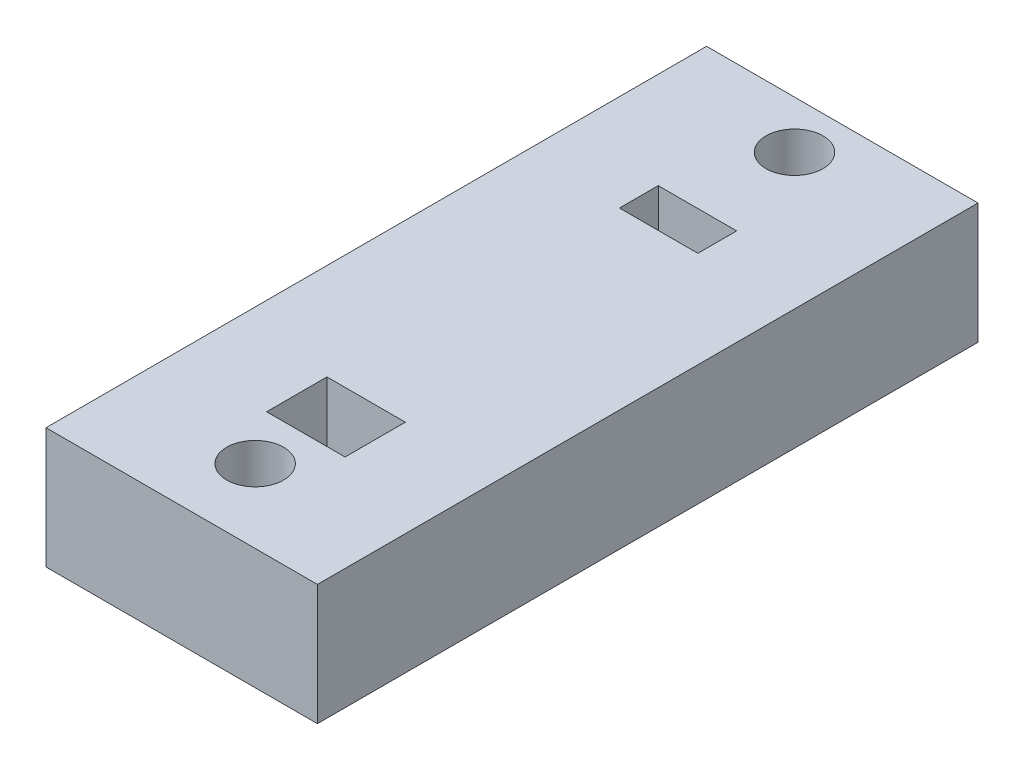
SolidWorks part; units mm, degrees
ref_plane "Front Plane" through (0, 0, 0) normal (0, 0, 1) x (1, 0, 0)
ref_plane "Top Plane" through (0, 0, 0) normal (0, 1, 0) x (1, 0, 0)
ref_plane "Right Plane" through (0, 0, 0) normal (1, 0, 0) x (0, 0, -1)
sketch "Sketch1" plane through (0, 0, 0) normal (0, 1, 0) x (1, 0, 0)
  line L0 (4.5, 4.1162) -> (4.5, 0) construction
  line L1 (0, 0) -> (9, 0)
  line L2 (0, 0) -> (0, 21.9046)
  line L3 (0, 21.9046) -> (9, 21.9046)
  line L4 (9, 0) -> (9, 21.9046)
  line L5 (3.2, 17.1021) -> (5.8, 17.1021)
  line L6 (3.2, 17.1021) -> (3.2, 15.8162)
  line L7 (3.2, 15.8162) -> (5.8, 15.8162)
  line L8 (5.8, 17.1021) -> (5.8, 15.8162)
  line L9 (3.2, 6.1162) -> (5.8, 6.1162)
  line L10 (3.2, 6.1162) -> (3.2, 4.1162)
  line L11 (3.2, 4.1162) -> (5.8, 4.1162)
  line L12 (5.8, 6.1162) -> (5.8, 4.1162)
  line L13 (4.5, 17.1021) -> (4.5, 21.9046) construction
  circle A0 centre (4.5, 20.32) radius 0.9439
  circle A1 centre (4.5, 2.4356) radius 0.9439
  dimension "D1" = 2.6
  dimension "D2" = 9
  dimension "D3" = 2
  dimension "D4" = 9.7
extrude "Boss-Extrude1" add sketch "Sketch1" along normal blind 4
